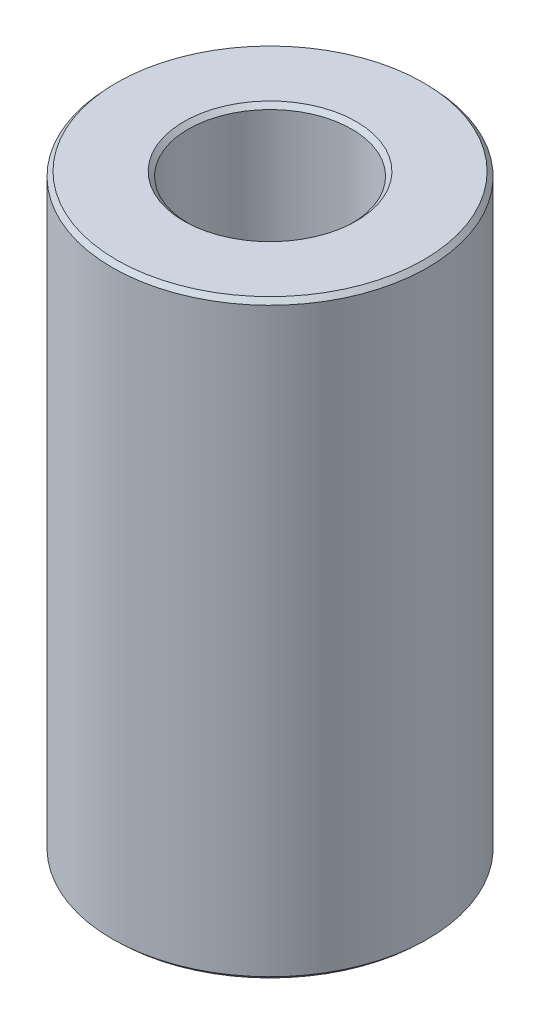
SolidWorks part; units mm, degrees
ref_plane "Front Plane" through (0, 0, 0) normal (0, 0, 1) x (1, 0, 0)
ref_plane "Top Plane" through (0, 0, 0) normal (0, 1, 0) x (1, 0, 0)
ref_plane "Right Plane" through (0, 0, 0) normal (1, 0, 0) x (0, 0, -1)
sketch "Sketch1" plane through (0, 0, 0) normal (0, 1, 0) x (1, 0, 0)
  circle A0 centre (0, 0) radius 45
  dimension "SLEEVE_OD" = 90
extrude "Boss-Extrude1" add sketch "Sketch1" along normal blind 168.3858
sketch "Sketch2" plane through (0, 0, 0) normal (0, 1, 0) x (1, 0, 0)
  circle A0 centre (0, 0) radius 23.3105
  dimension "BORE_D" = 46.6209
extrude "Cut-Extrude1" cut sketch "Sketch2" along normal through all
chamfer "Chamfer1" distance 1.2826 angle 43.333 4 edges at (0, 168.3858, 23.3105) (0, 0, 23.3105) (0, 0, 45) (0, 168.3858, 45) first distance on face at (0, 168.3858, 23.3105) first distance on face at (0, 0, 23.3105) first distance on face at (0, 168.3858, 45)
